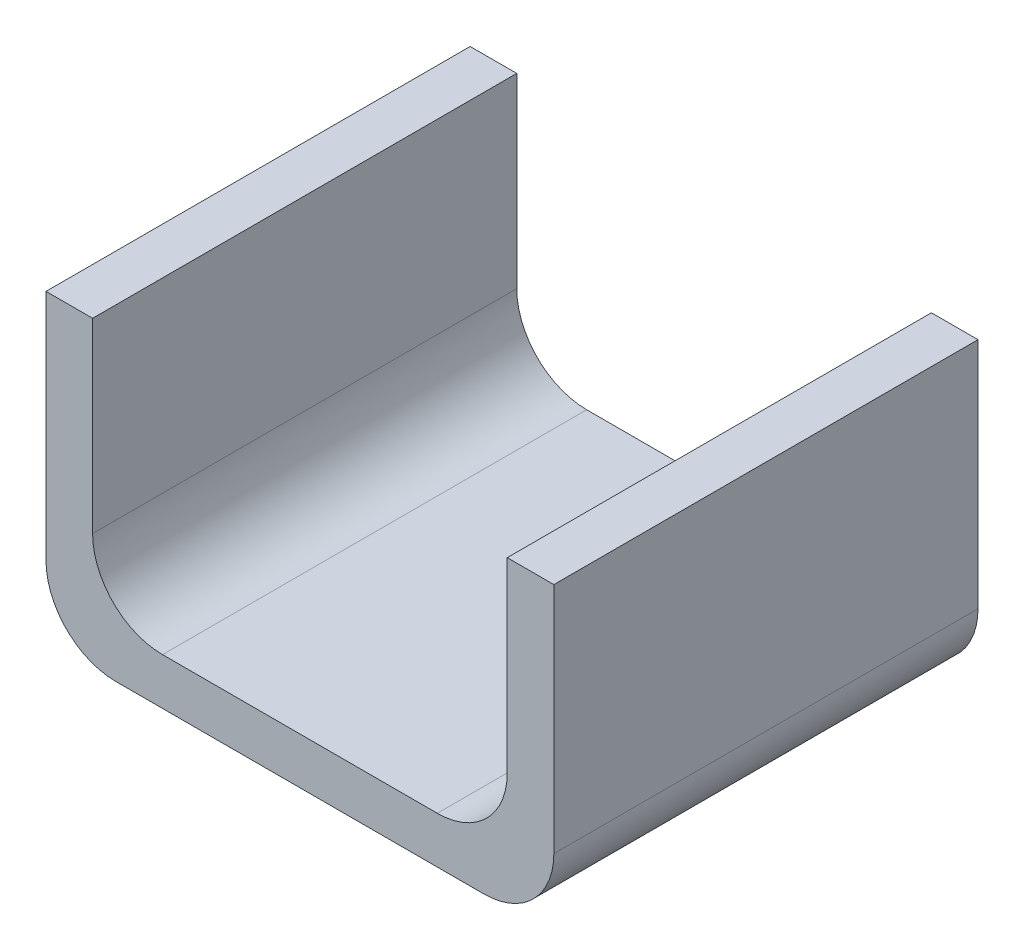
SolidWorks part; units mm, degrees
ref_plane "Front Plane" through (0, 0, 0) normal (0, 0, 1) x (1, 0, 0)
ref_plane "Top Plane" through (0, 0, 0) normal (0, 1, 0) x (1, 0, 0)
ref_plane "Right Plane" through (0, 0, 0) normal (1, 0, 0) x (0, 0, -1)
sketch "Sketch1" plane through (0, 0, 0) normal (0, 1, 0) x (1, 0, 0)
  line L0 (-8.9301, 6.8449) -> (-8.9301, -11.3562)
  line L1 (-10.9301, 6.8449) -> (10.8623, 6.8449)
  line L2 (-10.9301, 6.8449) -> (-10.9301, -11.3562)
  line L3 (-10.9301, -11.3562) -> (10.8623, -11.3562)
  line L4 (10.8623, 6.8449) -> (10.8623, -11.3562)
  line L5 (8.8623, 6.8449) -> (8.8623, -11.3562)
  line L6 (8.8623, 16.582) -> (8.8623, -11.418) construction
  dimension "D1" = 2
  dimension "D2" = 2
extrude "Boss-Extrude1" add sketch "Sketch1" along normal blind 2 contours L5 L1 L0 L3 | L2 L3 L0 L1 | L1 L5 L3 L4 region at (-0.0339, 0, 2.2556) region at (-9.9301, 0, 2.2556) region at (9.8623, 0, 2.2556)
extrude "Boss-Extrude2" add sketch "Sketch1<3>" along normal blind 13 contours L2 L3 L0 L1 | L1 L5 L3 L4 region at (-9.9301, 0, 2.2556) region at (9.8623, 0, 2.2556)
sketch "Sketch1<3>" plane through (0, 0, 0) normal (0, 1, 0) x (1, 0, 0) same geometry as "Sketch1"
fillet "Fillet1" radius 3 4 edges at (-10.9301, 0, 2.2556) (10.8623, 0, 2.2556) (-8.9301, 2, 2.2556) (8.8623, 2, 2.2556)
